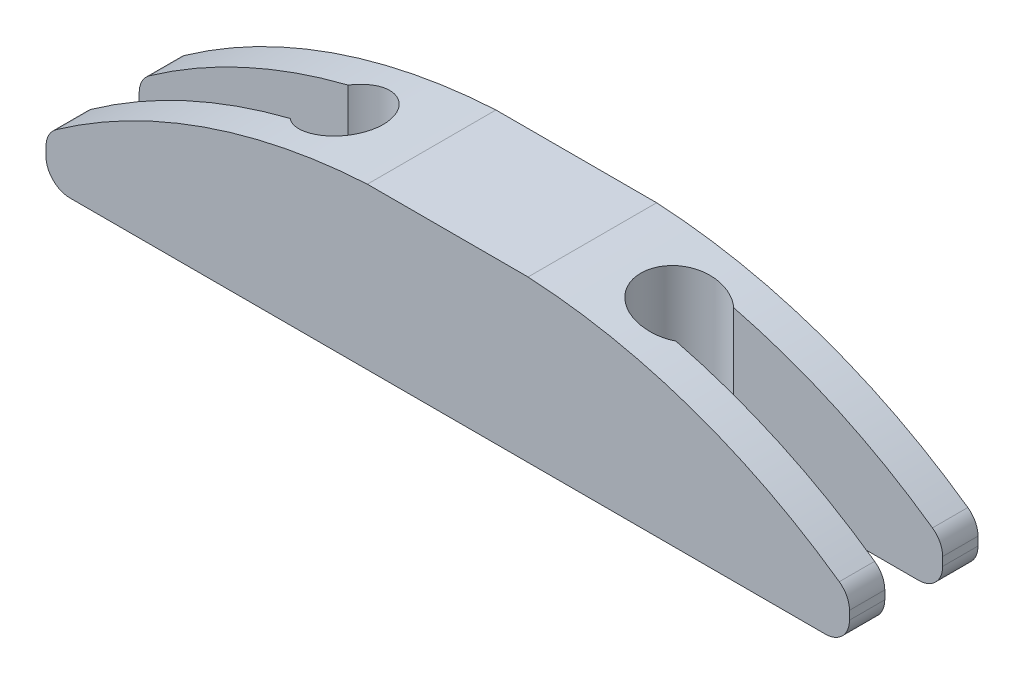
SolidWorks part; units mm, degrees
ref_plane "Front Plane" through (0, 0, 0) normal (0, 0, 1) x (1, 0, 0)
ref_plane "Top Plane" through (0, 0, 0) normal (0, 1, 0) x (1, 0, 0)
ref_plane "Right Plane" through (0, 0, 0) normal (1, 0, 0) x (0, 0, -1)
sketch "Sketch1" plane through (0, 0, 0) normal (0, 0, 1) x (1, 0, 0)
  line L0 (125, 0) -> (-125, 0)
  line L1 (-125, 0) -> (-125, 14)
  line L2 (0, 0) -> (0, 50) construction
  line L3 (-75, 0) -> (-75, 18) construction
  line L4 (25, 50) -> (-25, 50)
  line L5 (75, 0) -> (75, 18) construction
  line L6 (125, 0) -> (125, 14)
  circle A0 centre (-107, 14) radius 6
  circle A1 centre (-75, 18) radius 7
  arc A2 (-125, 14) -> (-25, 50) centre (-14.9778, -134.7283) cw
  arc A3 (125, 14) -> (25, 50) centre (14.9778, -134.7283) ccw
  circle A4 centre (75, 18) radius 7
  circle A5 centre (107, 14) radius 6
  dimension "D5" = 12
  dimension "D4" = 14
  dimension "D6" = 25
  dimension "D7" = 185
  dimension "D1" = 125
  dimension "D2" = 14
  dimension "D3" = 50
sketch "Sketch2" plane through (0, 0, 0) normal (0, 1, 0) x (1, 0, 0)
  line L0 (0, -20) -> (0, 20) construction
  line L1 (0, 20) -> (-125, 20)
  line L2 (-125, 20) -> (-125, 9)
  line L3 (0, 20) -> (125, 20)
  line L4 (125, 20) -> (125, 9)
  line L5 (-25, 20) -> (-25, -20)
  line L6 (125, 0) -> (-125, 0) construction
  line L7 (25, -20) -> (25, 20)
  line L9 (-125, 0) -> (-52.06, 0) construction
  line L12 (125, -20) -> (125, -9)
  line L13 (0, -20) -> (125, -20)
  line L14 (-125, -20) -> (-125, -9)
  line L15 (0, -20) -> (-125, -20)
  line L16 (-125, 0) -> (-25, 0) construction
  point P20 (0, 0)
  point P21 (25, 0)
  point P22 (-25, 0)
  dimension "D1" = 125
  dimension "D2" = 11
  dimension "D3" = 20
  dimension "D4" = 125
  dimension "D5" = 11
  dimension "D6" = 25
  dimension "D7" = 25
  dimension "D8" = 72.94
sketch "Sketch3" plane through (0, 0, 0) normal (0, 1, 0) x (1, 0, 0)
  line L0 (-125, 0) -> (-52.06, 0) construction
  line L2 (125, 0) -> (-125, 0) construction
  line L3 (-125, 9) -> (-125, -9)
  line L4 (-125, 9) -> (-59.9973, 9)
  line L5 (-125, -9) -> (-59.9973, -9)
  line L9 (0, 20) -> (0, -20) construction
  line L10 (125, 0) -> (52.06, 0) construction
  line L11 (125, -9) -> (59.9973, -9)
  line L12 (125, 9) -> (59.9973, 9)
  line L13 (125, 9) -> (125, -9)
  circle A2 centre (-16, 0) radius 8
  circle A3 centre (15.5228, 0) radius 8
  arc A5 (-59.9973, 9) -> (-59.9973, -9) centre (-52.06, 0) cw
  arc A8 (59.9973, 9) -> (59.9973, -9) centre (52.06, 0) ccw
  dimension "D1" = 12
  dimension "D2" = 16
  dimension "D3" = 16
extrude "Boss-Extrude1" add sketch "Sketch1" along normal blind 20 and the other way blind 20 contours A2 L4 A3 L6 L0 L1
fillet "Fillet4" radius 7.5 1 edges at (-125, 14, 0)
fillet "Fillet5" radius 7.5 1 edges at (125, 14, 0)
fillet "Fillet6" radius 7.5 1 edges at (125, 0, 0)
fillet "Fillet7" radius 7.5 1 edges at (-125, 0, 0)
sketch "Sketch4" plane through (0, 0, 0) normal (0, -1, 0) x (1, 0, 0)
  line L0 (-117.5, 20) -> (-117.5, -20) construction
  line L1 (-117.5, -20) -> (-117.5, 0) construction
  line L2 (-117.5, 0) -> (117.9211, 0) construction
  line L3 (125.0701, 0) -> (52.1301, 0) construction
  line L4 (117.5, 20) -> (117.5, -20) construction
extrude "Cut-Extrude6" cut sketch "Sketch3" along normal through all contours A5 L4 L3 L5 | L12 A8 L11 L13 region at (-81.8542, 0, 0) region at (81.8542, 0, 0)
